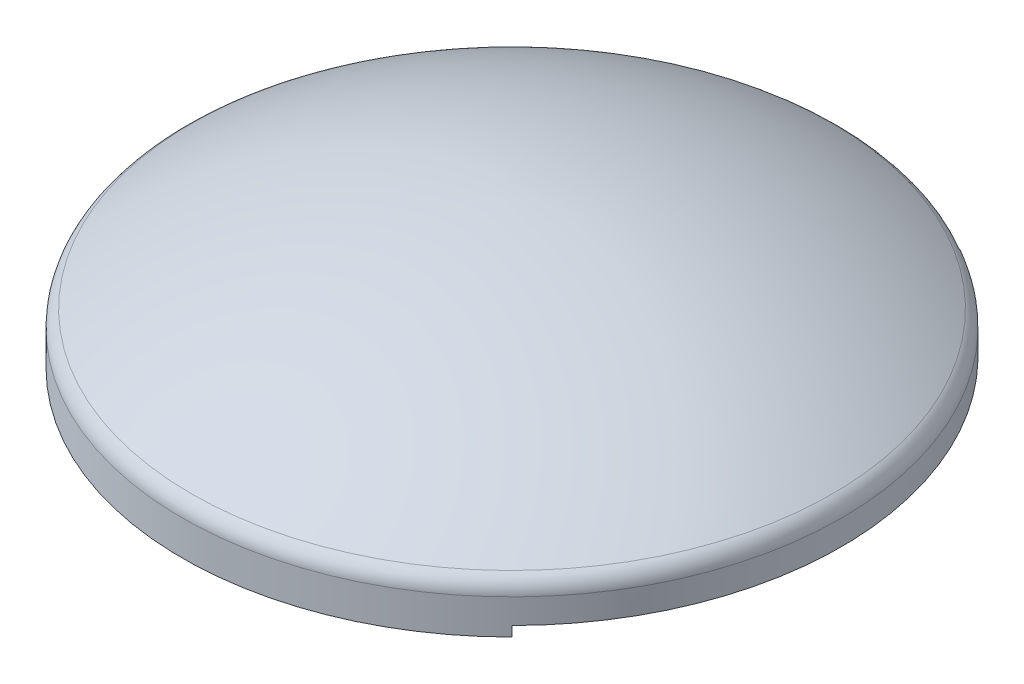
SolidWorks part; units mm, degrees
ref_plane "前视基准面" through (0, 0, 0) normal (0, 0, 1) x (1, 0, 0)
ref_plane "上视基准面" through (0, 0, 0) normal (0, 1, 0) x (1, 0, 0)
ref_plane "右视基准面" through (0, 0, 0) normal (1, 0, 0) x (0, 0, -1)
sketch "Sketch1" plane through (0, 0, 0) normal (1, 0, 0) x (0, 0, -1)
  line L0 (0, 0) -> (30, 0) construction
  line L1 (30, 3.54) -> (10, 3.54) construction
  line L2 (10, 3.54) -> (10, 10.04) construction
  line L3 (10, 10.04) -> (0, 10.04) construction
  line L4 (0, 10.04) -> (0, 0) construction
  line L5 (30, 3.54) -> (30, 0) construction
  line L6 (30, 0) -> (25, 0)
  line L7 (25, 0) -> (25, -1)
  line L8 (25, -1) -> (33, -1)
  line L9 (33, -1) -> (33, 3.54)
  line L10 (30, 0) -> (31.029, 0)
  line L11 (31.029, 0) -> (31.029, 3.5295)
  line L12 (0, -4.6308) -> (0, 9.0048) construction
  line L14 (0, 14.2213) -> (0, 13.24)
  arc A3 (33, 3.54) -> (0, 14.2213) centre (-1.1881, -45.7669) ccw
  arc A4 (31.029, 3.5295) -> (0, 13.24) centre (-1.7351, -46.7349) ccw
  point P8 (33, 3.54)
  point P11 (0, 13.24)
  dimension "D1" = 3.54
  dimension "D2" = 6.5
  dimension "D3" = 30
  dimension "D4" = 10
  dimension "D5" = 1
  dimension "D6" = 5
  dimension "D7" = 3.2
  dimension "D8" = 3
revolve "Revolve1" add sketch "Sketch1" angle 360 about L4 region at (0, -0.3634, -30.5145)
sketch "Sketch2" plane through (0, 0, 0) normal (1, 0, 0) x (0, 0, -1)
  line L9 (25, 0) -> (33, 0)
  line L10 (25, 0) -> (25, -1)
  line L11 (25, -1) -> (33, -1)
  line L12 (33, 0) -> (33, -1)
revolve "Cut-Revolve1" cut sketch "Sketch2" angle 270 mid plane about L4
fillet "Fillet1" radius 2 1 edges at (0, 3.54, 33)
sketch "Sketch3" plane through (0, 0, 0) normal (0, 0, 1) x (1, 0, 0)
  line L0 (0, -7.7237) -> (0, 17.403) construction
  line L1 (-16.5, 0) -> (16.5, 0)
  line L2 (16.5, 0) -> (16.5, 3.55)
  line L3 (16.5, 3.55) -> (-16.5, 3.55)
  line L4 (-16.5, 0) -> (-16.5, 3.55)
  point P8 (0, 0)
  point P9 (0, 3.55)
  dimension "D1" = 16.5
  dimension "D2" = 3.55
extrude "Cut-Extrude1" cut sketch "Sketch3" against normal up to next
